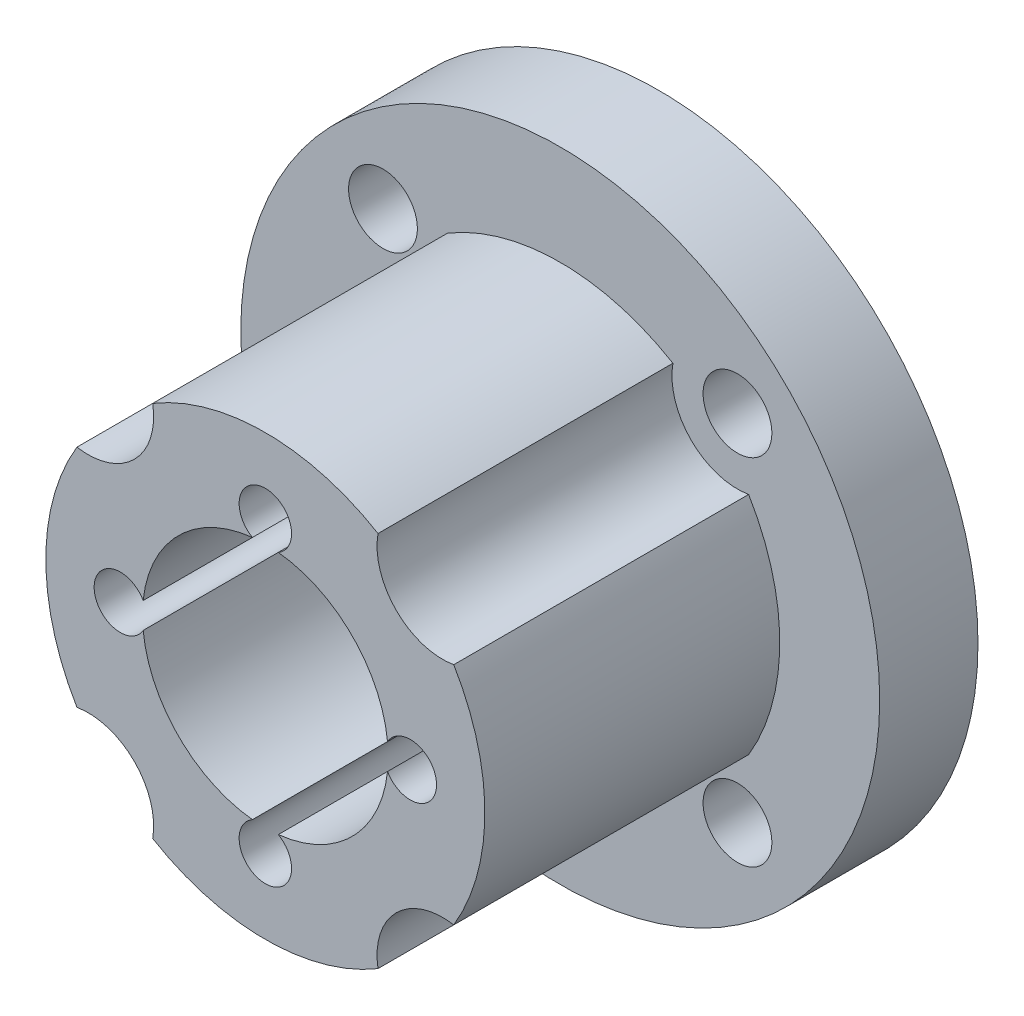
SolidWorks part; units mm, degrees
material "1.4003 (X2CrNi12)"
ref_plane "Ebene vorne" through (0, 0, 0) normal (0, 0, 1) x (1, 0, 0)
ref_plane "Ebene oben" through (0, 0, 0) normal (0, 1, 0) x (1, 0, 0)
ref_plane "Ebene rechts" through (0, 0, 0) normal (1, 0, 0) x (0, 0, -1)
sketch "Skizze1" plane through (0, 0, 0) normal (0, 0, 1) x (1, 0, 0)
  circle A0 centre (0, 0) radius 6.7
  circle A1 centre (0, 0) radius 3.75
  circle A2 centre (0, 0) radius 9.75
  dimension "D1" = 7.5
  dimension "D2" = 13.4
  dimension "D3" = 19.5
extrude "Aufsatz-Linear austragen1" add sketch "Skizze1" along normal blind 9 contours A0 A1 | A1 region at (-6.5105, 0, 0)
extrude "Aufsatz-Linear austragen2" add sketch "Skizze1<7>" against normal blind 3 contours A2 | A1
sketch "Skizze1<7>" plane through (0, 0, 0) normal (0, 0, 1) x (1, 0, 0) same geometry as "Skizze1"
hole_wizard "M2 Gewindebohrung1" positions "Skizze4" profile "Skizze3" tap size "M2" standard "DIN" end condition through all
sketch "Skizze4" plane through (0, 0, 9) normal (0, 0, 1) x (1, 0, 0)
  line L0 (0, 4.425) -> (0, -4.425) construction
  line L2 (4.425, 0) -> (-4.425, 0) construction
  point P0 (4.425, 0)
  point P2 (0, -4.425)
  point P4 (-4.425, 0)
  point P6 (0, 4.425)
  dimension "D1" = 8.85
cosmetic thread "Bohrungsgewinde1" parameters "D2"=2
cosmetic thread "Bohrungsgewinde2" parameters "D2"=2
cosmetic thread "Bohrungsgewinde3" parameters "D2"=2
cosmetic thread "Bohrungsgewinde4" parameters "D2"=2
sketch "Skizze3" plane through (4.425, 0, 9) normal (1, 0, 0) x (0, -1, 0)
  line L0 (0, 0) -> (0, 12)
  line L1 (0, 12) -> (0.8, 12)
  line L2 (0.8, 12) -> (0.8, 0)
  line L5 (0.8, 0) -> (0, 0)
  line L11 (0, -6.35) -> (0, 107.95) construction
  dimension "Bohrerdurchmesser" = 1.6
  dimension "Bohrungstiefe" = 12
sketch "Skizze5" plane through (0, 0, 9) normal (0, 0, 1) x (1, 0, 0)
  line L0 (-5.4094, 5.4094) -> (5.4094, -5.4094) construction
  line L1 (0, 9.75) -> (0, -9.75) construction
  line L2 (5.4094, 5.4094) -> (-5.4094, -5.4094) construction
  circle A0 centre (5.4094, 5.4094) radius 1.05
  circle A1 centre (5.4094, -5.4094) radius 1.05
  circle A2 centre (-5.4094, -5.4094) radius 1.05
  circle A3 centre (-5.4094, 5.4094) radius 1.05
  circle A4 centre (0, 0) radius 9.75 construction
  circle A5 centre (-5.4094, 5.4094) radius 2
  circle A6 centre (5.4094, 5.4094) radius 2
  circle A7 centre (5.4094, -5.4094) radius 2
  circle A8 centre (-5.4094, -5.4094) radius 2
  dimension "D1" = 2.1
  dimension "D4" = 4
  dimension "D2" = 15.3
  dimension "D3" = 45
extrude "Schnitt-Linear austragen1" cut sketch "Skizze5" against normal through all contours A3 | A0 | A1 | A2
extrude "Schnitt-Linear austragen2" cut sketch "Skizze5<3>" against normal up to surface (9 mm away) up to face at (0, 0, 0)
sketch "Skizze5<3>" plane through (0, 0, 9) normal (0, 0, 1) x (1, 0, 0) same geometry as "Skizze5"
